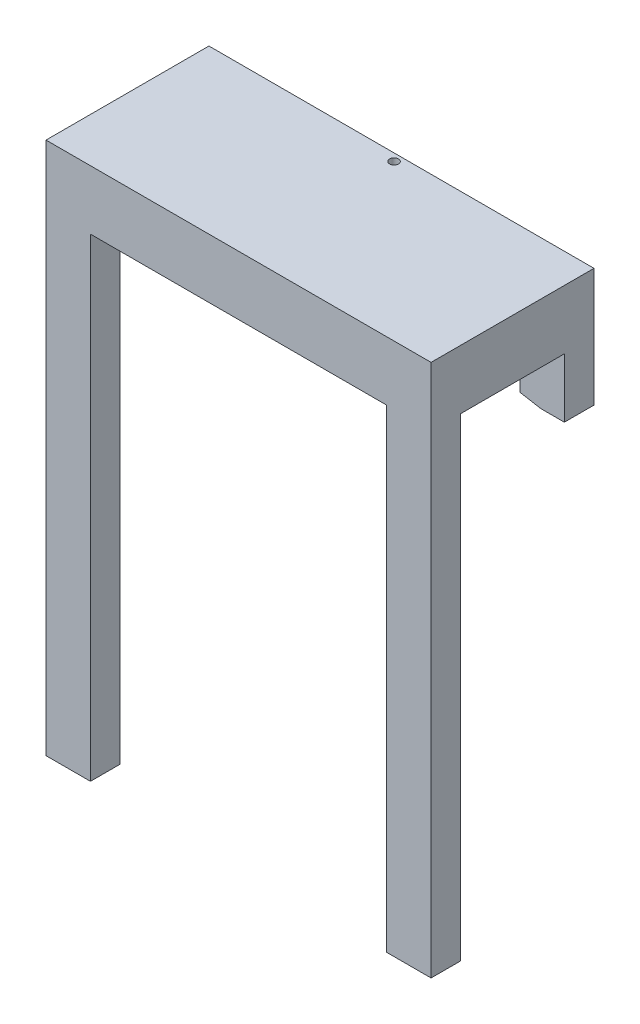
SolidWorks part; units mm, degrees
ref_plane "Front Plane" through (0, 0, 0) normal (0, 0, 1) x (1, 0, 0)
ref_plane "Top Plane" through (0, 0, 0) normal (0, 1, 0) x (1, 0, 0)
ref_plane "Right Plane" through (0, 0, 0) normal (1, 0, 0) x (0, 0, -1)
sketch "Sketch1" plane through (0, 0, 0) normal (0, 0, 1) x (1, 0, 0)
  line L1 (-82.55, -114.3) -> (82.55, -114.3)
  line L2 (-82.55, -114.3) -> (-82.55, 114.3)
  line L3 (-82.55, 114.3) -> (82.55, 114.3)
  line L4 (82.55, -114.3) -> (82.55, 114.3)
  line L5 (-82.55, -114.3) -> (82.55, 114.3) construction
  line L6 (-82.55, 114.3) -> (82.55, -114.3) construction
  point P0 (0, 0)
  dimension "D1" = 228.6
  dimension "D2" = 165.1
extrude "Boss-Extrude1" add sketch "Sketch1" along normal blind 12.7
sketch "Sketch2" plane through (0, 0, 12.7) normal (0, 0, 1) x (1, 0, 0)
  line L0 (-82.55, -114.3) -> (82.55, -114.3) construction
  line L1 (-63.5, -114.3) -> (63.5, -114.3)
  line L2 (-63.5, -114.3) -> (-63.5, 88.9)
  line L3 (-63.5, 88.9) -> (63.5, 88.9)
  line L4 (63.5, -114.3) -> (63.5, 88.9)
  line L5 (-82.55, 114.3) -> (-82.55, -114.3) construction
  dimension "D1" = 203.2
  dimension "D2" = 127
  dimension "D3" = 19.05
extrude "Cut-Extrude1" cut sketch "Sketch2" against normal through all
sketch "Sketch3" plane through (0, 0, 0) normal (0, 0, -1) x (-1, 0, 0)
  line L0 (82.55, 114.3) -> (82.55, -114.3) construction
  line L1 (-82.55, 114.3) -> (82.55, 114.3)
  line L2 (-82.55, 114.3) -> (-82.55, 88.9)
  line L3 (-82.55, 88.9) -> (82.55, 88.9)
  line L4 (82.55, 114.3) -> (82.55, 88.9)
  dimension "D1" = 25.4
extrude "Boss-Extrude2" add sketch "Sketch3" along normal blind 57.15
sketch "Sketch4" plane through (0, 0, -57.15) normal (0, 0, -1) x (-1, 0, 0)
  line L0 (-63.5, -114.3) -> (-63.5, 88.9) construction
  line L1 (-82.55, 88.9) -> (-63.5, 88.9)
  line L2 (-82.55, 88.9) -> (-82.55, 63.5)
  line L3 (-82.55, 63.5) -> (-63.5, 63.5)
  line L4 (-63.5, 88.9) -> (-63.5, 63.5)
  dimension "D1" = 25.4
extrude "Boss-Extrude3" add sketch "Sketch4" against normal blind 12.7
mirror "Mirror1" about plane through (0, 0, 0) normal (1, 0, 0) of "Boss-Extrude3"
sketch "Sketch5" plane through (0, 0, -57.15) normal (0, 0, -1) x (-1, 0, 0)
  line L5 (-72.5032, 63.5) -> (-63.5, 65.0875)
  line L6 (-82.55, 63.5) -> (-63.5, 63.5) construction
  line L7 (-63.5, 63.5) -> (-63.5, 88.9) construction
  line L8 (-63.5, 65.0875) -> (-63.5, 63.5)
  line L9 (-63.5, 63.5) -> (-72.5032, 63.5)
  dimension "D1" = 1.5875
  dimension "D2" = 80
extrude "Cut-Extrude2" cut sketch "Sketch5" against normal up to next
mirror "Mirror2" about plane through (0, 0, 0) normal (1, 0, 0) of "Cut-Extrude2"
sketch "Sketch6" plane through (0, 114.3, 0) normal (0, 1, 0) x (1, 0, 0)
  line L0 (-82.55, 57.15) -> (82.55, 57.15) construction
  circle A0 centre (0, 53.975) radius 1.8986
  dimension "D1" = 3.7973
  dimension "D2" = 3.175
extrude "Cut-Extrude3" cut sketch "Sketch6" against normal up to next
